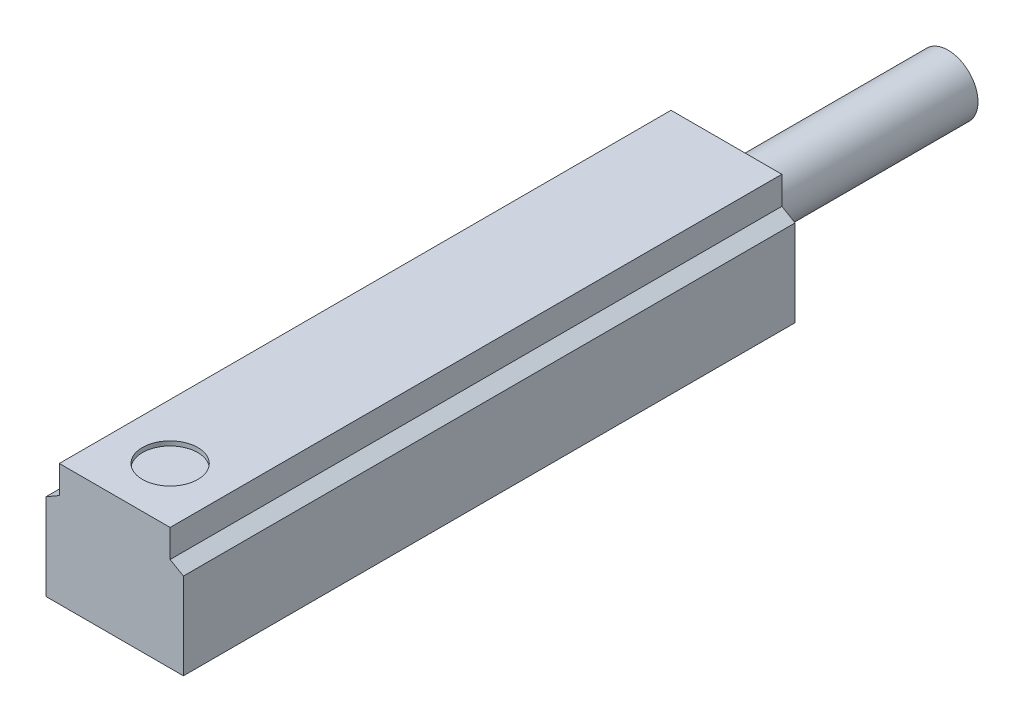
SolidWorks part; units mm, degrees
ref_plane "前视基准面" through (0, 0, 0) normal (0, 0, 1) x (1, 0, 0)
ref_plane "上视基准面" through (0, 0, 0) normal (0, 1, 0) x (1, 0, 0)
ref_plane "右视基准面" through (0, 0, 0) normal (1, 0, 0) x (0, 0, -1)
sketch "草图1" plane through (0, 0, 0) normal (0, 0, 1) x (1, 0, 0)
  line L0 (-3.1, 0) -> (3.1, 0)
  line L1 (3.1, 0) -> (3.1, 3.9)
  line L2 (3.1, 3.9) -> (2.5, 4.2464)
  line L3 (2.5, 4.2464) -> (2.5, 5.5)
  line L4 (2.5, 5.5) -> (-2.5, 5.5)
  line L5 (-2.5, 5.5) -> (-2.5, 4.2464)
  line L6 (-2.5, 4.2464) -> (-3.1, 3.9)
  line L7 (-3.1, 3.9) -> (-3.1, 0)
extrude "凸台-拉伸1" add sketch "草图1" against normal blind 27.6
sketch "草图2" plane through (0, 0, 0) normal (1, 0, 0) x (0, 0, -1)
  line L0 (27.6, 2.75) -> (27.6, 4.1)
  line L1 (27.6, 4.1) -> (37.6, 4.1)
  line L2 (37.6, 4.1) -> (37.6, 2.75)
  line L3 (37.6, 2.75) -> (27.6, 2.75)
  line L4 (37.6, 2.75) -> (27.6, 2.75) construction
revolve "旋转1" add sketch "草图2" angle 360 about L4 reverse direction yes
sketch "草图3" plane through (0, 0, 0) normal (1, 0, 0) x (0, 0, -1)
  line L0 (2.5, 5.5) -> (3.75, 5.5)
  line L1 (3.75, 5.5) -> (3.75, 5.3)
  line L2 (3.75, 5.3) -> (2.5, 5.3)
  line L3 (2.5, 5.3) -> (2.5, 5.5)
  line L4 (2.5, 5.3) -> (2.5, 5.5) construction
revolve "切除-旋转1" cut sketch "草图3" angle 360 about L4 reverse direction yes
ref_plane "SW1_BODY XY" through (0, 0, 0) normal (0, 0, 1) x (1, 0, 0)
ref_plane "SW1_BODY XZ" through (0, 0, 0) normal (0, -1, 0) x (-1, 0, 0)
ref_plane "SW1_BODY YZ" through (0, 0, 0) normal (1, 0, 0) x (0, 0, -1)
ref_axis "SW1_BODY X" through (-80.9, 0, 0) along (1, 0, 0)
ref_axis "SW1_BODY Y" through (0, -50, 0) along (0, 1, 0)
ref_axis "SW1_BODY Z" through (0, 0, 80.9) along (0, 0, -1)
sketch3d "SW1_BODY"
  point P0 (0, 0, 0)
ref_plane "SW2_BODY XY" through (0, 0, 0) normal (0, 0, -1) x (-1, 0, 0)
ref_plane "SW2_BODY XZ" through (0, 0, 0) normal (0, 1, 0) x (1, 0, 0)
ref_plane "SW2_BODY YZ" through (0, 0, 0) normal (1, 0, 0) x (0, 0, -1)
ref_axis "SW2_BODY X" through (-80.9, 0, 0) along (1, 0, 0)
ref_axis "SW2_BODY Y" through (0, 50, 0) along (0, -1, 0)
ref_axis "SW2_BODY Z" through (0, 0, -80.9) along (0, 0, 1)
sketch3d "SW2_BODY"
  point P0 (0, 0, 0)
